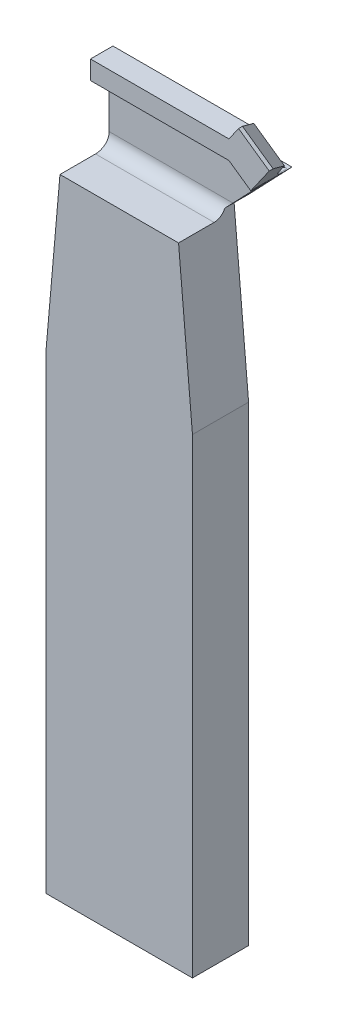
SolidWorks part; units mm, degrees
ref_plane "Front Plane" through (0, 0, 0) normal (0, 0, 1) x (1, 0, 0)
ref_plane "Top Plane" through (0, 0, 0) normal (0, 1, 0) x (1, 0, 0)
ref_plane "Right Plane" through (0, 0, 0) normal (1, 0, 0) x (0, 0, -1)
sketch "Sketch1" plane through (0, 0, 0) normal (0, 0, 1) x (1, 0, 0)
  line L0 (0, 0) -> (0, 10)
  line L1 (0, 10) -> (74, 10)
  line L2 (74, 10) -> (79.1622, 17.3724)
  line L3 (79.1622, 17.3724) -> (95.5452, 5.9008)
  line L5 (0, 0) -> (74, 0)
  line L6 (74, 0) -> (85.6846, -8.1816)
  line L8 (85.6846, -8.1816) -> (95.5452, 5.9008)
  dimension "D1" = 125
extrude "Boss-Extrude1" add sketch "Sketch1" along normal blind 12
sketch "Sketch2" plane through (61.3393, -42.9503, 0) normal (0.8192, -0.5736, 0) x (0, 0, -1)
  line L1 (-12, 59.6362) -> (0, 59.6362) construction
  line L3 (0, 42.4447) -> (0, 59.6362) construction
  line L4 (0, 52.9046) -> (0, 59.6362)
  line L5 (0, 52.9046) -> (-9.9341, 59.6362)
  line L6 (-9.9341, 59.6362) -> (0, 59.6362)
extrude "Cut-Extrude1" cut sketch "Sketch2" against normal through all
sketch "Sketch3" plane through (0, 0, 0) normal (0, -1, 0) x (-1, 0, 0)
  line L0 (-37, -12) -> (-37, 0)
  line L1 (0, -12) -> (-74, -12) construction
  line L2 (0, 0) -> (-74, 0) construction
  line L3 (0, -12) -> (0, 0) construction
  line L4 (-72, -2) -> (-2, -2)
  line L5 (-72, -2) -> (-72, -10)
  line L6 (-72, -10) -> (-2, -10)
  line L7 (-2, -2) -> (-2, -10)
  line L8 (-72, -2) -> (-2, -10) construction
  line L9 (-72, -10) -> (-2, -2) construction
  point P6 (-37, -6)
  dimension "D1" = 2
  dimension "D2" = 2
extrude "Cut-Extrude2" cut sketch "Sketch3" against normal blind 6 contours L7 L4 L0 L6 | L5 L6 L0 L4 region at (54.5, 0, 6) region at (19.5, 0, 6)
sketch "Sketch4" plane through (0, 0, 0) normal (0, -1, 0) x (1, 0, 0)
  line L0 (74, 10) -> (74, 2)
  line L1 (74, 12) -> (74, 0) construction
  line L2 (74, 2) -> (72, 2)
  line L3 (72, 2) -> (72, 10)
  line L4 (72, 10) -> (74, 10)
extrude "Cut-Extrude3" cut sketch "Sketch4" against normal blind 6
sketch "Sketch5" plane through (24.3453, 34.7686, 0) normal (-0.5736, -0.8192, 0) x (-0.8192, 0.5736, 0)
  line L0 (-74.8815, -12) -> (-74.8815, 0) construction
  line L1 (-60.6173, -10) -> (-72.8815, -10)
  line L2 (-60.6173, -10) -> (-60.6173, -2)
  line L3 (-60.6173, -2) -> (-72.8815, -2)
  line L4 (-72.8815, -10) -> (-72.8815, -2)
  dimension "D1" = 2
extrude "Cut-Extrude4" cut sketch "Sketch5" against normal blind 6
sketch "Sketch6" plane through (24.3453, 34.7686, 0) normal (-0.5736, -0.8192, 0) x (0.8192, -0.5736, 0)
  line L1 (72.8815, 10) -> (57.1758, 10)
  line L2 (72.8815, 10) -> (72.8815, 2)
  line L3 (72.8815, 2) -> (57.1758, 2)
  line L4 (57.1758, 10) -> (57.1758, 2)
extrude "Cut-Extrude5" cut sketch "Sketch6" against normal blind 6
sketch "Sketch7" plane through (0, 0, 0) normal (0, 0, -1) x (-1, 0, 0)
  line L1 (-74, -20) -> (0, -20)
  line L2 (0, -20) -> (0, 0)
  line L3 (0, 0) -> (-74, 0)
  line L4 (-74, -20) -> (-85.6846, -8.1816)
  line L7 (-85.6846, -8.1816) -> (-74, 0)
extrude "Boss-Extrude2" add sketch "Sketch7" against normal blind 2 contours L4 L7 L3 L2 L1
sketch "Sketch8" plane through (0, 0, 0) normal (0, 0, -1) x (-1, 0, 0)
  line L0 (-74, -20) -> (-85.6846, -8.1816)
  line L1 (-85.6846, -8.1816) -> (0, -8.1816)
  line L2 (0, 10) -> (0, -20) construction
  line L3 (-74, -20) -> (0, -20)
  line L4 (0, -20) -> (0, -8.1816)
extrude "Boss-Extrude3" add sketch "Sketch8" along normal blind 10
sketch "Sketch9" plane through (0, -8.1816, 0) normal (0, 1, 0) x (1, 0, 0)
  line L6 (0, 9) -> (85.6846, 9)
  line L7 (1, 9) -> (84.6846, 9)
  line L9 (1, 10) -> (1, 0)
  line L10 (1, 9) -> (1, 1)
  line L12 (0, 1) -> (85.6846, 1)
  line L13 (1, 1) -> (84.6846, 1)
  line L16 (84.6846, 10) -> (84.6846, 0)
  line L17 (84.6846, 9) -> (84.6846, 1)
  dimension "D1" = 1
  dimension "D2" = 1
  dimension "D3" = 1
  dimension "D4" = 1
sketch "Sketch12" plane through (0, 0, -10) normal (0, 0, -1) x (-1, 0, 0)
  line L0 (-74, -20) -> (-62.7738, -32.1496)
  line L1 (-62.7738, -32.1496) -> (0, -32.1496)
  line L2 (0, -32.1496) -> (0, -20)
  line L3 (0, -20) -> (-74, -20)
extrude "Boss-Extrude4" add sketch "Sketch12" against normal up to surface (12 mm away) up to face at (48.3841, -3.8447, 2)
sketch "Sketch15" plane through (0, -32.1496, 0) normal (0, -1, 0) x (1, 0, 0)
  line L2 (62.7738, -8) -> (0, -8)
  line L3 (60.7738, -8) -> (2, -8)
  line L5 (2, 2) -> (2, -10)
  line L6 (2, 0) -> (2, -8)
  line L8 (62.7738, 0) -> (0, 0)
  line L9 (60.7738, 0) -> (2, 0)
  line L11 (60.7738, 2) -> (60.7738, -10)
  line L12 (60.7738, 0) -> (60.7738, -8)
  dimension "D1" = 2
  dimension "D2" = 2
  dimension "D3" = 2
  dimension "D4" = 2
extrude "Cut-Extrude7" cut sketch "Sketch15" against normal through all
sketch "Sketch16" plane through (0, 0, 0) normal (0, 0, -1) x (-1, 0, 0)
  line L0 (-62.7738, -32.1496) -> (-85.6846, -8.1816)
  line L1 (-85.6846, -8.1816) -> (-60.7738, -8.1816)
  line L2 (-60.7738, -8.1816) -> (-62.7738, -32.1496)
extrude "Boss-Extrude5" add sketch "Sketch16" along normal blind 10 and the other way up to surface (2 mm away) other way up to face at (49.6923, -7.5224, 2)
sketch "Sketch17" plane through (0, 0, 0) normal (0, 0, -1) x (-1, 0, 0)
  line L1 (-60.7738, -8.1816) -> (-85.6846, -8.1816) construction
  line L2 (-84.2388, -6.7997) -> (-61.3281, -30.7676)
  line L3 (-84.2388, -6.7997) -> (-61.3281, -30.7676)
  line L4 (-60.7738, -8.1816) -> (-82.9178, -8.1816)
  line L5 (-60.7738, -8.1816) -> (-61.3281, -30.7676)
  line M9 (-85.6846, -8.1816) -> (-60.7738, -8.1816)
  dimension "D1" = 2
extrude "Cut-Extrude8" cut sketch "Sketch17" along normal up to surface (8 mm away) contours L5 L3 M9 region at (68.3399, -15.7103, 0) up to face at (31.3869, -20.1656, -8)
sketch "Sketch18" plane through (0, 0, 0) normal (0, 0, -1) x (-1, 0, 0)
  line L0 (-61.3281, -30.7676) -> (-58.4425, -33.7863)
  line L3 (-58.4425, -33.7863) -> (-58.4425, -8.1816)
  line L4 (0, -8.1816) -> (-85.6846, -8.1816) construction
  line L5 (-58.4425, -8.1816) -> (-82.9178, -8.1816)
  line L6 (-82.9178, -8.1816) -> (-61.3281, -30.7676)
extrude "Cut-Extrude9" cut sketch "Sketch18" along normal up to surface (8 mm away) up to face at (31.3869, -20.1656, -8)
fillet "Fillet3" radius 5 1 edges at (82.9178, -8.1816, -4)
fillet "Fillet4" radius 5 1 edges at (1, -8.1816, 0)
fillet "Fillet5" radius 5 3 edges at (71.1073, -20.5371, 0) (83.0899, -8.5841, 0) (85.3699, -8.1816, 0)
fillet "Fillet6" radius 2 2 edges at (60.7738, -31.3474, -6.5) (60.7738, -29.2281, -1.4645)
sketch "Sketch20" plane through (0, 0, 2) normal (0, 0, 1) x (1, 0, 0)
  line L0 (0, -32.1496) -> (-7.7367, -120.5804)
  line L1 (0, -32.1496) -> (62.7738, -32.1496)
  line L2 (62.7738, -32.1496) -> (70.5105, -120.5804)
  line L37 (70.5105, -120.5804) -> (70.5105, -292.1685)
  line L38 (-7.7367, -120.5804) -> (-7.7367, -292.1685)
  line L41 (-7.7367, -292.1685) -> (-7.7367, -372.1408)
  line L42 (-7.7367, -372.1408) -> (70.5105, -372.1408)
  line L43 (70.5105, -372.1408) -> (70.5105, -292.1685)
  dimension "D1" = 95
  dimension "D2" = 95
extrude "Boss-Extrude6" add sketch "Sketch20" against normal blind 4
fillet "Fillet7" radius 4 1 edges at (31.3869, -32.1496, -2)
fillet "Fillet9" radius 7 1 edges at (31.3869, -32.1496, 0)
sketch "Sketch21" plane through (0, 0, -2) normal (0, 0, -1) x (-1, 0, 0)
  line L5 (5.7367, -370.1408) -> (5.7367, -120.5804)
  line L6 (-60.7738, -35.6137) -> (0.3031, -35.6137)
  line L7 (0, -32.1496) -> (7.7367, -120.5804) construction
  line L8 (0.3031, -35.6137) -> (7.7367, -120.5804)
  line L9 (7.7367, -120.5804) -> (7.7367, -372.1408)
  line L10 (7.7367, -120.5804) -> (7.7367, -372.1408) construction
  line L11 (7.7367, -372.1408) -> (-70.5105, -372.1408)
  line L12 (-70.5105, -372.1408) -> (-70.5105, -120.5804)
  line L13 (-70.5105, -120.5804) -> (-63.0769, -35.6137)
  line L14 (-70.5105, -120.5804) -> (-62.7738, -32.1496) construction
  line L15 (-63.0769, -35.6137) -> (-60.7738, -35.6137)
extrude "Boss-Extrude9" add sketch "Sketch21" against normal blind 30 contours L15 L6 region at (31.3869, -207.3164, -2)
sketch "Sketch22" plane through (0, 0, -2) normal (0, 0, -1) x (-1, 0, 0)
  line L2 (7.7367, -370.1408) -> (-70.5105, -370.1408)
  line L3 (5.7367, -370.1408) -> (-68.5105, -370.1408)
  line L5 (-68.5105, -372.1408) -> (-68.5105, -120.5804)
  line L6 (-68.5105, -370.1408) -> (-68.5105, -120.6677)
  line L8 (5.7367, -120.5804) -> (5.7367, -372.1408)
  line L9 (5.7367, -120.6677) -> (5.7367, -370.1408)
  line L11 (-1.9924, -32.3239) -> (5.7443, -120.7547)
  line L12 (-1.5296, -37.6137) -> (5.7367, -120.6677)
  line L14 (-68.5181, -120.7547) -> (-60.7814, -32.3239)
  line L15 (-68.5105, -120.6677) -> (-61.2442, -37.6137)
  line L16 (-61.2442, -37.6137) -> (-60.7738, -37.6137)
  line L17 (-2, -37.6137) -> (-60.7738, -37.6137)
  line L18 (-2, -37.6137) -> (-60.7738, -37.6137)
  line L19 (-2, -37.6137) -> (-1.5296, -37.6137)
  dimension "D1" = 2
  dimension "D2" = 2
  dimension "D3" = 2
  dimension "D4" = 2
  dimension "D5" = 2
  dimension "D6" = 2
extrude "Cut-Extrude10" cut sketch "Sketch22" against normal blind 28
sketch "Sketch23" plane through (0, 0, -2) normal (0, 0, -1) x (-1, 0, 0)
  line L0 (7.7367, -372.1408) -> (-70.5105, -372.1408) construction
  line L1 (-68.5105, -370.1408) -> (5.6563, -370.1408)
  line L2 (-68.5105, -370.1408) -> (-68.5105, -372.1408)
  line L3 (-68.5105, -372.1408) -> (5.6563, -372.1408)
  line L4 (5.6563, -370.1408) -> (5.6563, -372.1408)
extrude "Cut-Extrude11" cut sketch "Sketch23" against normal up to surface (28 mm away) up to face at (31.3869, -176.1408, 26)
fillet "Fillet10" radius 7 1 edges at (31.3869, -35.6137, 2)
